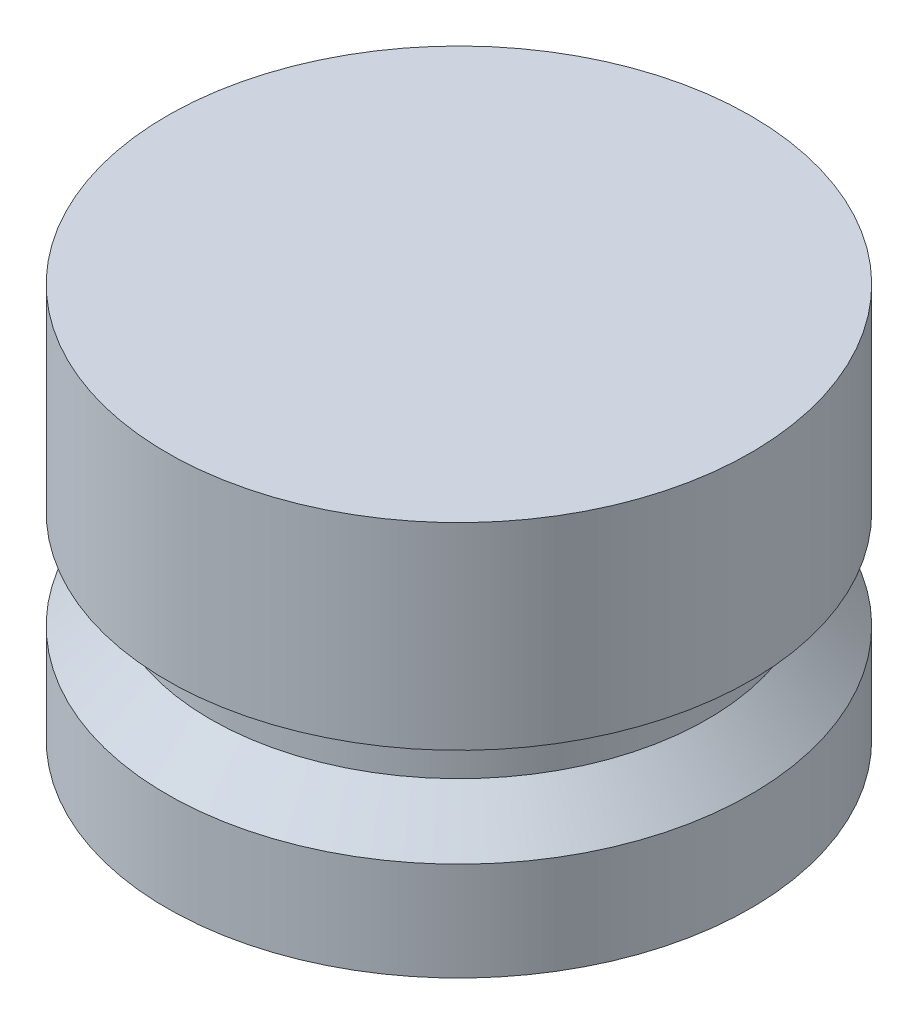
SolidWorks part; units mm, degrees
ref_plane "Front Plane" through (0, 0, 0) normal (0, 0, 1) x (1, 0, 0)
ref_plane "Top Plane" through (0, 0, 0) normal (0, 1, 0) x (1, 0, 0)
ref_plane "Right Plane" through (0, 0, 0) normal (1, 0, 0) x (0, 0, -1)
sketch "Sketch1" plane through (0, 0, 0) normal (0, 0, 1) x (1, 0, 0)
  line L0 (0, 0) -> (0, 12.7) construction
  line L1 (0, 0) -> (-9.398, 0)
  line L2 (-9.398, 0) -> (-9.398, 3.175)
  line L4 (-8.001, 4.572) -> (-8.001, 6.35)
  line L5 (-8.001, 6.35) -> (-9.398, 6.35)
  line L6 (-9.398, 6.35) -> (-9.398, 12.7)
  line L7 (-9.398, 12.7) -> (0, 12.7)
  line L8 (-9.525, 16.6801) -> (-9.525, -9.6051) construction
  line L9 (0, 0) -> (0, 12.7)
  line L10 (-8.001, 4.572) -> (-9.398, 3.175)
  dimension "D1" = 12.7
  dimension "D2" = 9.398
  dimension "D3" = 1.778
  dimension "D4" = 3.175
  dimension "D5" = 9.525
  dimension "D6" = 8.001
  dimension "D7" = 6.35
revolve "Revolve1" add sketch "Sketch1" angle 360 about L9
